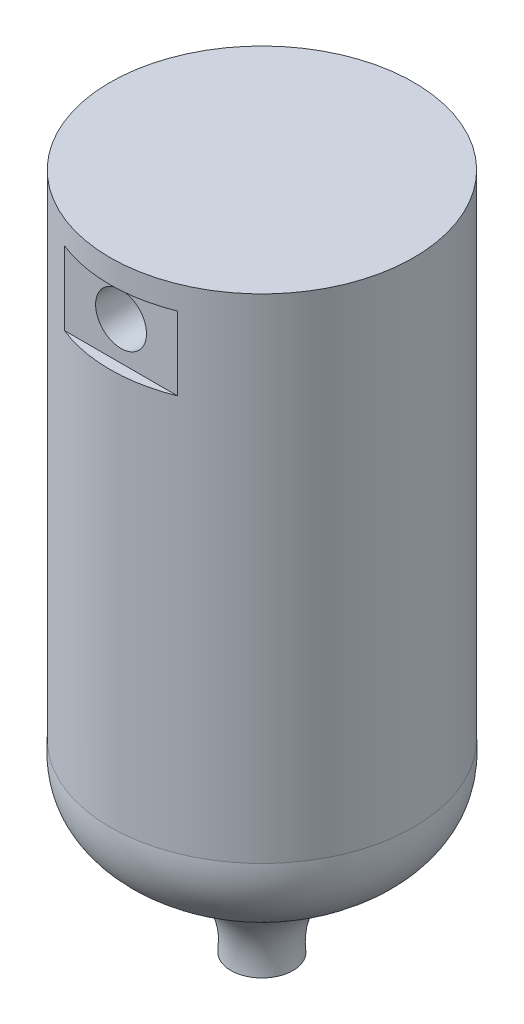
SolidWorks part; units mm, degrees
ref_plane "Front Plane" through (0, 0, 0) normal (0, 0, 1) x (1, 0, 0)
ref_plane "Top Plane" through (0, 0, 0) normal (0, 1, 0) x (1, 0, 0)
ref_plane "Right Plane" through (0, 0, 0) normal (1, 0, 0) x (0, 0, -1)
sketch "Sketch2" plane through (0, 0, 0) normal (0, 0, 1) x (1, 0, 0)
  line L1 (-3.8791, 0) -> (-3.8791, -12)
  line L4 (0, 0) -> (0, -10.1137) construction
  line L6 (-0.7951, -17.3166) -> (0, -17.3166)
  line L7 (-3.8791, 0) -> (0, 0)
  line L8 (0, 0) -> (0, -17.3166)
  spline S0 degree 1 poles (-3.8791, -12) (-3.8791, -12.6028) knots 0 0 1 1
  spline S1 degree 3 poles (-3.8791, -12.6028) (-4.0962, -15.2492) (-0.5373, -14.7278) (-0.7951, -17.3166) knots 0 0 0 0 1 1 1 1
  dimension "D4" = 0.6028
  dimension "D5" = 6.0234
  dimension "D1" = 17.3166
  dimension "D2" = 12
  dimension "D3" = 3.8791
  dimension "D6" = 1
  dimension "D7" = 1.3983
  dimension "D8" = 0.6858
  dimension "D9" = 2.0099
  dimension "D10" = 0.7951
revolve "Revolve1" add sketch "Sketch2" angle 360 about L4
ref_plane "Plane1" through (0, 0, 3.9) normal (0, 0, 1) x (1, 0, 0)
sketch "Sketch3" plane through (0, 0, 3.9) normal (0, 0, 1) x (1, 0, 0)
  circle A0 centre (0, -1.5) radius 0.65
  dimension "D1" = 1.3
  dimension "D2" = 1.5
extrude "Cut-Extrude1" cut sketch "Sketch3" against normal blind 2
ref_plane "Plane2" through (0, 0, -3.9) normal (0, 0, 1) x (1, 0, 0)
sketch "Sketch4" plane through (0, 0, -3.9) normal (0, 0, 1) x (1, 0, 0)
  circle A0 centre (0, -1.5) radius 0.65 construction
  circle A1 centre (0, -1.5) radius 0.65
extrude "Cut-Extrude2" cut sketch "Sketch4" along normal blind 2
sketch "Sketch5" plane through (0, -17.3166, 0) normal (0, -1, 0) x (1, 0, 0)
  point P0 (0, 0)
sketch "Sketch6" plane through (0, 0, 0) normal (1, 0, 0) x (0, 0, -1)
  line L4 (0, 0) -> (0, -9.7034) construction
  line L5 (-3.5997, -2.4763) -> (-3.5997, -0.5998)
  line L6 (-4.1704, -2.4763) -> (-3.5997, -2.4763)
  line L7 (-4.1704, -0.5998) -> (-4.1704, -2.4763)
  line L8 (-3.5997, -0.5998) -> (-4.1704, -0.5998)
extrude "Cut-Extrude4" cut sketch "Sketch6" against normal blind 5 and the other way blind 5
